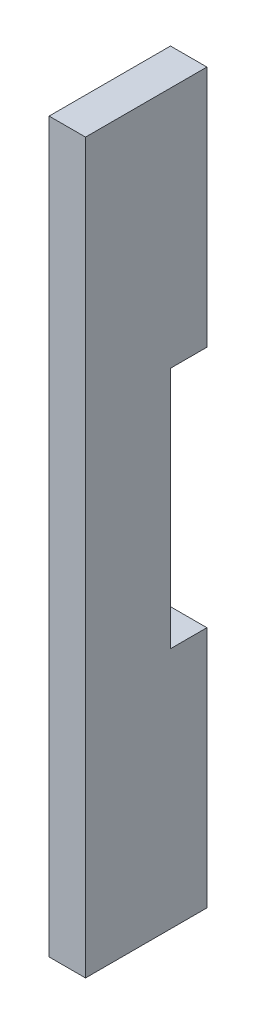
SolidWorks part; units mm, degrees
ref_plane "Alzado" through (0, 0, 0) normal (0, 0, 1) x (1, 0, 0)
ref_plane "Planta" through (0, 0, 0) normal (0, 1, 0) x (1, 0, 0)
ref_plane "Vista lateral" through (0, 0, 0) normal (1, 0, 0) x (0, 0, -1)
sketch "Croquis1" plane through (0, 0, 0) normal (1, 0, 0) x (0, 0, -1)
  line L1 (0, 0) -> (20, 0)
  line L2 (0, 0) -> (0, 120)
  line L3 (0, 120) -> (20, 120)
  line L4 (20, 0) -> (20, 120)
  dimension "D1" = 120
  dimension "D2" = 20
extrude "Saliente-Extruir1" add sketch "Croquis1" along normal blind 6
sketch "Croquis3" plane through (0, 0, 0) normal (1, 0, 0) x (0, 0, -1)
  line L0 (20, 0) -> (20, 120) construction
  line L1 (20, 39.99) -> (13.98, 39.99)
  line L2 (20, 39.99) -> (20, 80.01)
  line L3 (20, 80.01) -> (13.98, 80.01)
  line L4 (13.98, 39.99) -> (13.98, 80.01)
  line L5 (0, 120) -> (0, 0) construction
  point P6 (0, 60)
  point P9 (13.98, 60)
  dimension "D1" = 6.02
  dimension "D2" = 40.02
extrude "Cortar-Extruir1" cut sketch "Croquis3" along normal through all
